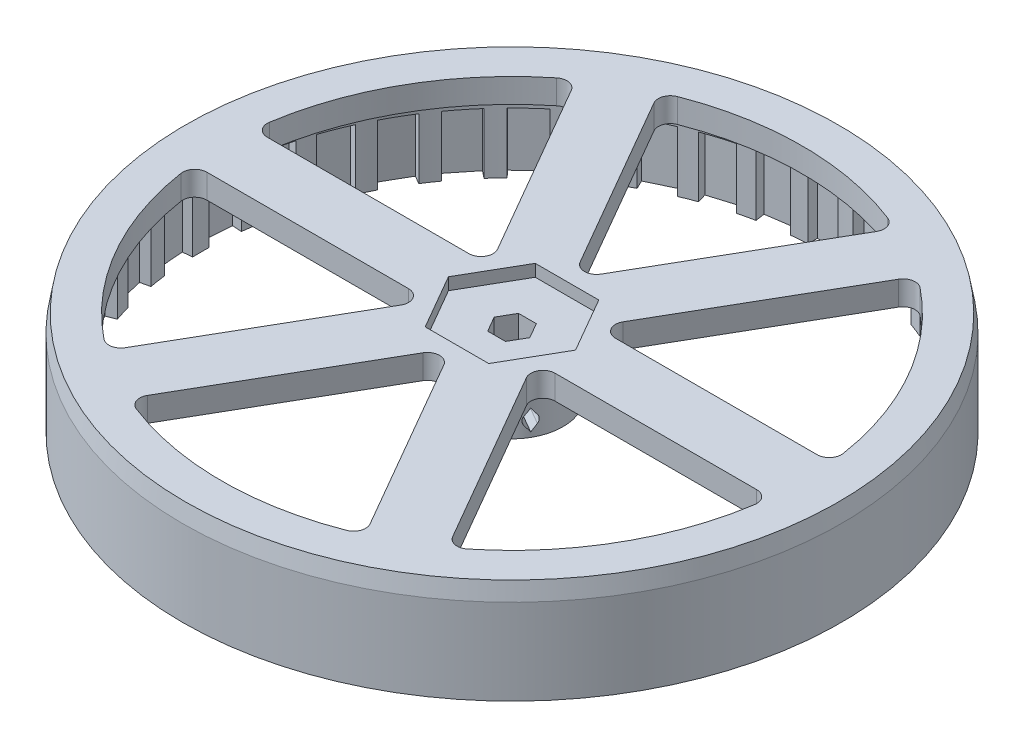
SolidWorks part; units mm, degrees
material "ABS"
ref_plane "Front Plane" through (0, 0, 0) normal (0, 0, 1) x (1, 0, 0)
ref_plane "Top Plane" through (0, 0, 0) normal (0, 1, 0) x (1, 0, 0)
ref_plane "Right Plane" through (0, 0, 0) normal (1, 0, 0) x (0, 0, -1)
sketch "Sketch1" plane through (0, 0, 0) normal (0, 0, 1) x (1, 0, 0)
  line L0 (0, 29) -> (0, 33)
  line L4 (51.5, 29) -> (51.5, 16)
  line L5 (51.5, 16) -> (54.5, 16)
  line L6 (54.5, 16) -> (54.5, 33)
  line L7 (54.5, 33) -> (0, 33)
  line L8 (0, 0) -> (0, 63.0003) construction
  line L11 (0, 29) -> (51.5, 29)
  dimension "D3" = 103
  dimension "D4" = 3
  dimension "D7" = 13
  dimension "D8" = 4
revolve "Main Revolve" add sketch "Sketch1" angle 360 about L8
sketch "Sketch2" plane through (0, 33, 0) normal (0, 1, 0) x (1, 0, 0)
  line L0 (0, 0) -> (0, 75.8468) construction
  line L1 (0, 0) -> (27.25, 47.1984) construction
  line L2 (18.402, 41.8732) -> (1.7321, 13)
  line L3 (-18.402, 41.8732) -> (-1.7321, 13)
  line L4 (0, 0) -> (-27.25, 47.1984) construction
  arc A0 (-17.3947, 44.7373) -> (17.3947, 44.7373) centre (0, 0) cw
  circle A2 centre (0, 0) radius 54.5 construction
  arc A3 (17.3947, 44.7373) -> (18.402, 41.8732) centre (16.67, 42.8732) cw
  arc A6 (-17.3947, 44.7373) -> (-18.402, 41.8732) centre (-16.67, 42.8732) ccw
  arc A8 (1.7321, 13) -> (-1.7321, 13) centre (0, 14) cw
  point P15 (0, 10)
  point P23 (0, 10)
  dimension "D5" = 48
  dimension "D6" = 2
  dimension "D7" = 2
  dimension "D3" = 2
  dimension "D1" = 30
  dimension "D2" = 30
  dimension "D4" = 10
extrude "Slot Cut" cut sketch "Sketch2" against normal through all
pattern_circular "Slot Cut Pattern" count 6 over 360 about axis through (0, 33, 0) along (0, -1, 0) of "Slot Cut"
sketch "Sketch4" plane through (0, 16, 0) normal (0, -1, 0) x (1, 0, 0)
  line L0 (-2.5, 53) -> (2.5, 53)
  line L1 (-2.5, 53) -> (-2.5, 51.4393)
  line L2 (2.5, 53) -> (2.5, 51.4393)
  circle A0 centre (0, 0) radius 51.5 construction
  arc A1 (2.5, 51.4393) -> (-2.5, 51.4393) centre (0, 0) ccw
  point P3 (0, 53)
  dimension "D2" = 1.5
  dimension "D1" = 5
extrude "Magnet Slots" cut sketch "Sketch4" against normal blind 10
pattern_circular "Magnet Cut Pattern" count 42 over 360 about axis through (0, 16, 0) along (0, -1, 0) of "Magnet Slots"
chamfer "Chamfer1" distance 0.5 angle 80 1 edges at (0, 33, -54.5) first distance on face at (0, 33, 33.6578)
sketch "Sketch5" plane through (0, 33, 0) normal (0, 1, 0) x (1, 0, 0)
  line L1 (2.9445, 0) -> (1.4722, 2.55)
  line L2 (1.4722, 2.55) -> (-1.4722, 2.55)
  line L3 (-1.4722, 2.55) -> (-2.9445, 0)
  line L4 (-2.9445, 0) -> (-1.4722, -2.55)
  line L5 (-1.4722, -2.55) -> (1.4722, -2.55)
  line L6 (1.4722, -2.55) -> (2.9445, 0)
  circle A0 centre (0, 0) radius 2.55 construction
  dimension "D1" = 5.1
extrude "Cut-Extrude1" cut sketch "Sketch5" against normal through all both and the other way through all
sketch "Sketch8" plane through (0, 29, 0) normal (0, -1, 0) x (1, 0, 0)
  line L0 (-1.4722, 2.55) -> (1.4722, 2.55) construction
  line L1 (2.9445, 0) -> (1.4722, 2.55)
  line L2 (1.4722, 2.55) -> (-1.4722, 2.55)
  line L3 (-1.4722, 2.55) -> (-2.9445, 0)
  line L4 (-2.9445, 0) -> (-1.4722, -2.55)
  line L5 (-1.4722, -2.55) -> (1.4722, -2.55)
  line L6 (1.4722, -2.55) -> (2.9445, 0)
  circle A0 centre (0, 0) radius 2.55 construction
  circle A1 centre (0, 0) radius 8.45
  dimension "D1" = 16.9
extrude "Boss-Extrude1" add sketch "Sketch8" along normal blind 8
sketch "Sketch9" plane through (0, 29, 0) normal (0, -1, 0) x (1, 0, 0)
  circle A0 centre (0, 0) radius 8.45
  circle A1 centre (0, 0) radius 8.95
  circle A2 centre (0, 0) radius 8.45 construction
  dimension "D1" = 0.5
extrude "Boss-Extrude2" add sketch "Sketch9" along normal blind 1
sketch "Sketch10" plane through (-2.2084, 0, -1.275) normal (0.866, 0, 0.5) x (0.5, 0, -0.866)
  line L0 (0, 26) -> (0, 21) construction
  line L2 (-1.4722, 21) -> (1.4722, 21) construction
  line L4 (2, 26) -> (-2, 26)
  line L5 (2, 26) -> (2, 21)
  line L6 (2, 21) -> (-2, 21)
  line L7 (-2, 26) -> (-2, 21)
  line L8 (2, 26) -> (-2, 21) construction
  line L9 (2, 21) -> (-2, 26) construction
  point P6 (0, 23.5)
  dimension "D1" = 4
  dimension "D2" = 5
extrude "Cut-Extrude2" cut sketch "Sketch10" against normal blind 1.6 and the other way blind 1.6
extrude "Cut-Extrude3" cut sketch "Sketch10<2>" along normal blind 1.6 and the other way blind 1.6 from surface starting at face at (2.2084, 27, 1.275)
sketch "Sketch10<2>" plane through (-2.2084, 0, -1.275) normal (0.866, 0, 0.5) x (0.5, 0, -0.866) same geometry as "Sketch10"
fillet "Fillet1" radius 0.5 4 edges at (-0.4167, 23.5, -2.55) (2.4167, 23.5, -0.9141) (0.4167, 23.5, 2.55) (-2.4167, 23.5, 0.9141)
sketch "Sketch11" plane through (-3.594, 0, -2.075) normal (0.866, 0, 0.5) x (0.5, 0, -0.866)
  line L0 (0, 26) -> (0, 21) construction
  line L1 (2, 26) -> (-2, 26) construction
  line L2 (-2, 21) -> (2, 21) construction
  line L3 (0, 23.5) -> (0, 21.8) construction
  line L4 (0, 21.8) -> (-0.8258, 22.8515)
  line L5 (0, 21.8) -> (0.8258, 22.8515)
  line L6 (0, 23.5) -> (0.5997, 23.5) construction
  line L7 (0, 25.2) -> (-0.8258, 24.1485)
  line L8 (0, 25.2) -> (0.8258, 24.1485)
  arc A0 (-0.8258, 24.1485) -> (-0.8258, 22.8515) centre (0, 23.5) ccw
  arc A1 (0.8258, 22.8515) -> (0.8258, 24.1485) centre (0, 23.5) ccw
  dimension "D1" = 2.1
  dimension "D2" = 1.7
extrude "Cut-Extrude4" cut sketch "Sketch11" against normal up to next and the other way blind 15.5 contours L7 A0 L4 L5 A1 L8
sketch "Sketch14" plane through (0, 33, 0) normal (0, 1, 0) x (1, 0, 0)
  line L0 (2.9445, 0) -> (1.4722, 2.55) construction
  line L1 (5.2539, -9.1) -> (10.5078, 0)
  line L2 (10.5078, 0) -> (5.2539, 9.1)
  line L3 (5.2539, 9.1) -> (-5.2539, 9.1)
  line L4 (-5.2539, 9.1) -> (-10.5078, 0)
  line L5 (-10.5078, 0) -> (-5.2539, -9.1)
  line L6 (-5.2539, -9.1) -> (5.2539, -9.1)
  circle A3 centre (0, 0) radius 9.1 construction
  dimension "D1" = 18.2
extrude "Cut-Extrude6" cut sketch "Sketch14" against normal blind 2
equation "\"D3@Sketch1\"=100+2*(1+0.5)"
